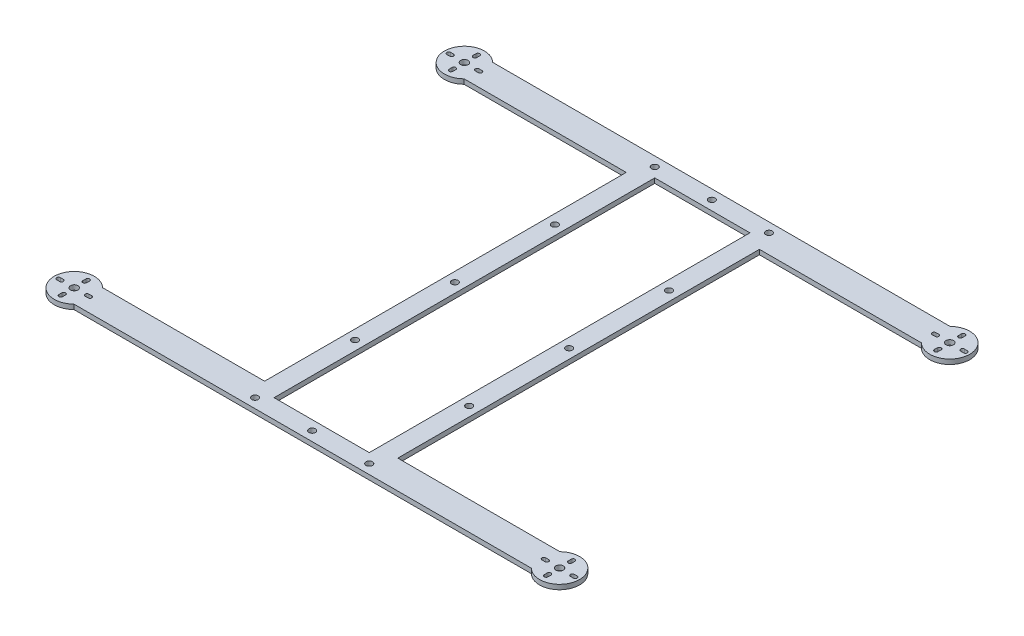
SolidWorks part; units mm, degrees
ref_plane "Front Plane" through (0, 0, 0) normal (0, 0, 1) x (1, 0, 0)
ref_plane "Top Plane" through (0, 0, 0) normal (0, 1, 0) x (1, 0, 0)
ref_plane "Right Plane" through (0, 0, 0) normal (1, 0, 0) x (0, 0, -1)
sketch "Sketch1" plane through (0, 0, 0) normal (0, 1, 0) x (1, 0, 0)
  line L1 (-44.45, 139.7) -> (44.45, 139.7)
  line L2 (-44.45, 120.65) -> (-44.45, -120.65)
  line L3 (-44.45, -139.7) -> (44.45, -139.7)
  line L4 (44.45, 120.65) -> (44.45, -120.65)
  line L5 (44.45, 139.7) -> (161.925, 139.7)
  line L7 (44.45, 120.65) -> (161.925, 120.65)
  line L8 (161.925, 139.7) -> (161.925, 120.65)
  line L14 (0, 0) -> (0, 187.5455) construction
  line L17 (0, 0) -> (-239.6804, 0) construction
  line L21 (0, 0) -> (44.45, 0) construction
  line L22 (-44.45, 120.65) -> (-161.925, 120.65)
  line L23 (-44.45, 139.7) -> (-161.925, 139.7)
  line L24 (-161.925, 139.7) -> (-161.925, 120.65)
  line L37 (-31.75, 127) -> (31.75, 127)
  line L40 (-31.75, 127) -> (-31.75, -127)
  line L43 (-31.75, -127) -> (31.75, -127)
  line L46 (31.75, 127) -> (31.75, -127)
  line L49 (44.45, -120.65) -> (161.925, -120.65)
  line L50 (44.45, -139.7) -> (161.925, -139.7)
  line L51 (161.925, -139.7) -> (161.925, -120.65)
  line L88 (-161.925, -139.7) -> (-161.925, -120.65)
  line L89 (-44.45, -139.7) -> (-161.925, -139.7)
  line L90 (-44.45, -120.65) -> (-161.925, -120.65)
  point P4 (0, 139.7)
  point P6 (-44.45, 0)
  dimension "D4" = 117.475
  dimension "D1" = 279.4
  dimension "D2" = 88.9
  dimension "D3" = 19.05
  dimension "D6" = 12.7
  dimension "D7" = 12.7
  dimension "D8" = 12.7
  dimension "D10" = 117.475
  dimension "D12" = 12.7
  dimension "D18" = 19.05
extrude "Boss-Extrude1" add sketch "Sketch1" along normal blind 3.175
sketch "Sketch4" plane through (0, 3.175, 0) normal (0, 1, 0) x (1, 0, 0)
  line L0 (161.925, 120.65) -> (161.925, 139.7) construction
  line L1 (-161.925, 139.7) -> (-161.925, 120.65) construction
  line L2 (-161.925, -120.65) -> (-161.925, -139.7) construction
  line L3 (161.925, -139.7) -> (161.925, -120.65) construction
  circle A0 centre (161.925, 130.175) radius 13.335
  circle A1 centre (-161.925, 130.175) radius 13.335
  circle A2 centre (-161.925, -130.175) radius 13.335
  circle A3 centre (161.925, -130.175) radius 13.335
  point P18 (161.925, -130.175)
extrude "Boss-Extrude4" add sketch "Sketch4" against normal up to surface (3.175 mm away) up to face at (0, 0, 0)
sketch "Sketch5" plane through (0, 3.175, 0) normal (0, 1, 0) x (1, 0, 0)
  line L0 (151.425, 130.175) -> (153.425, 130.175) construction
  line L1 (151.425, 131.425) -> (153.425, 131.425)
  line L2 (151.425, 128.925) -> (153.425, 128.925)
  line L3 (161.925, 130.175) -> (161.925, 143.51) construction
  line L4 (172.425, 130.175) -> (170.425, 130.175) construction
  line L5 (172.425, 131.425) -> (170.425, 131.425)
  line L6 (172.425, 128.925) -> (170.425, 128.925)
  line L7 (161.925, 139.175) -> (161.925, 137.175) construction
  line L8 (163.175, 139.175) -> (163.175, 137.175)
  line L9 (160.675, 139.175) -> (160.675, 137.175)
  line L10 (161.925, 130.175) -> (175.26, 130.175) construction
  line L11 (161.925, 121.175) -> (161.925, 123.175) construction
  line L12 (163.175, 121.175) -> (163.175, 123.175)
  line L13 (160.675, 121.175) -> (160.675, 123.175)
  line L14 (0, 0) -> (0, 263.0018) construction
  line L15 (0, 0) -> (558.7896, 0) construction
  line L16 (-151.425, 130.175) -> (-153.425, 130.175) construction
  line L17 (-151.425, 131.425) -> (-153.425, 131.425)
  line L18 (-151.425, 128.925) -> (-153.425, 128.925)
  line L19 (-172.425, 130.175) -> (-170.425, 130.175) construction
  line L20 (-172.425, 131.425) -> (-170.425, 131.425)
  line L21 (-172.425, 128.925) -> (-170.425, 128.925)
  line L22 (-161.925, 139.175) -> (-161.925, 137.175) construction
  line L23 (-163.175, 139.175) -> (-163.175, 137.175)
  line L24 (-160.675, 139.175) -> (-160.675, 137.175)
  line L25 (-161.925, 121.175) -> (-161.925, 123.175) construction
  line L26 (-163.175, 121.175) -> (-163.175, 123.175)
  line L27 (-160.675, 121.175) -> (-160.675, 123.175)
  line L28 (-161.925, 130.175) -> (-175.26, 130.175) construction
  line L29 (-161.925, 130.175) -> (-161.925, 143.51) construction
  line L30 (151.425, -130.175) -> (153.425, -130.175) construction
  line L31 (151.425, -131.425) -> (153.425, -131.425)
  line L32 (151.425, -128.925) -> (153.425, -128.925)
  line L33 (161.925, -139.175) -> (161.925, -137.175) construction
  line L34 (163.175, -139.175) -> (163.175, -137.175)
  line L35 (160.675, -139.175) -> (160.675, -137.175)
  line L36 (172.425, -130.175) -> (170.425, -130.175) construction
  line L37 (172.425, -131.425) -> (170.425, -131.425)
  line L38 (172.425, -128.925) -> (170.425, -128.925)
  line L39 (161.925, -121.175) -> (161.925, -123.175) construction
  line L40 (163.175, -121.175) -> (163.175, -123.175)
  line L41 (160.675, -121.175) -> (160.675, -123.175)
  line L42 (161.925, -130.175) -> (175.26, -130.175) construction
  line L43 (161.925, -130.175) -> (161.925, -143.51) construction
  line L44 (-161.925, -130.175) -> (-161.925, -143.51) construction
  line L45 (-161.925, -130.175) -> (-175.26, -130.175) construction
  line L46 (-161.925, -121.175) -> (-161.925, -123.175) construction
  line L47 (-163.175, -121.175) -> (-163.175, -123.175)
  line L48 (-160.675, -121.175) -> (-160.675, -123.175)
  line L49 (-161.925, -139.175) -> (-161.925, -137.175) construction
  line L50 (-163.175, -139.175) -> (-163.175, -137.175)
  line L51 (-160.675, -139.175) -> (-160.675, -137.175)
  line L52 (-172.425, -130.175) -> (-170.425, -130.175) construction
  line L53 (-172.425, -131.425) -> (-170.425, -131.425)
  line L54 (-172.425, -128.925) -> (-170.425, -128.925)
  line L55 (-151.425, -130.175) -> (-153.425, -130.175) construction
  line L56 (-151.425, -131.425) -> (-153.425, -131.425)
  line L57 (-151.425, -128.925) -> (-153.425, -128.925)
  circle A0 centre (161.925, 130.175) radius 2.5
  arc A1 (151.425, 131.425) -> (151.425, 128.925) centre (151.425, 130.175) ccw
  arc A2 (153.425, 128.925) -> (153.425, 131.425) centre (153.425, 130.175) ccw
  arc A3 (152.5924, 120.65) -> (152.5924, 139.7) centre (161.925, 130.175) ccw construction
  arc A4 (172.425, 131.425) -> (172.425, 128.925) centre (172.425, 130.175) cw
  arc A5 (170.425, 128.925) -> (170.425, 131.425) centre (170.425, 130.175) cw
  arc A6 (163.175, 139.175) -> (160.675, 139.175) centre (161.925, 139.175) ccw
  arc A7 (160.675, 137.175) -> (163.175, 137.175) centre (161.925, 137.175) ccw
  arc A8 (163.175, 121.175) -> (160.675, 121.175) centre (161.925, 121.175) cw
  arc A9 (160.675, 123.175) -> (163.175, 123.175) centre (161.925, 123.175) cw
  arc A10 (-151.425, 131.425) -> (-151.425, 128.925) centre (-151.425, 130.175) cw
  arc A11 (-153.425, 128.925) -> (-153.425, 131.425) centre (-153.425, 130.175) cw
  arc A12 (-172.425, 131.425) -> (-172.425, 128.925) centre (-172.425, 130.175) ccw
  arc A13 (-170.425, 128.925) -> (-170.425, 131.425) centre (-170.425, 130.175) ccw
  arc A14 (-163.175, 139.175) -> (-160.675, 139.175) centre (-161.925, 139.175) cw
  arc A15 (-160.675, 137.175) -> (-163.175, 137.175) centre (-161.925, 137.175) cw
  arc A16 (-163.175, 121.175) -> (-160.675, 121.175) centre (-161.925, 121.175) ccw
  arc A17 (-160.675, 123.175) -> (-163.175, 123.175) centre (-161.925, 123.175) ccw
  circle A18 centre (-161.925, 130.175) radius 2.5
  arc A19 (151.425, -131.425) -> (151.425, -128.925) centre (151.425, -130.175) cw
  arc A20 (153.425, -128.925) -> (153.425, -131.425) centre (153.425, -130.175) cw
  arc A21 (163.175, -139.175) -> (160.675, -139.175) centre (161.925, -139.175) cw
  arc A22 (160.675, -137.175) -> (163.175, -137.175) centre (161.925, -137.175) cw
  arc A23 (172.425, -131.425) -> (172.425, -128.925) centre (172.425, -130.175) ccw
  arc A24 (170.425, -128.925) -> (170.425, -131.425) centre (170.425, -130.175) ccw
  arc A25 (163.175, -121.175) -> (160.675, -121.175) centre (161.925, -121.175) ccw
  arc A26 (160.675, -123.175) -> (163.175, -123.175) centre (161.925, -123.175) ccw
  circle A27 centre (161.925, -130.175) radius 2.5
  circle A28 centre (-161.925, -130.175) radius 2.5
  arc A29 (-163.175, -121.175) -> (-160.675, -121.175) centre (-161.925, -121.175) cw
  arc A30 (-160.675, -123.175) -> (-163.175, -123.175) centre (-161.925, -123.175) cw
  arc A31 (-163.175, -139.175) -> (-160.675, -139.175) centre (-161.925, -139.175) ccw
  arc A32 (-160.675, -137.175) -> (-163.175, -137.175) centre (-161.925, -137.175) ccw
  arc A33 (-172.425, -131.425) -> (-172.425, -128.925) centre (-172.425, -130.175) cw
  arc A34 (-170.425, -128.925) -> (-170.425, -131.425) centre (-170.425, -130.175) cw
  arc A35 (-151.425, -131.425) -> (-151.425, -128.925) centre (-151.425, -130.175) ccw
  arc A36 (-153.425, -128.925) -> (-153.425, -131.425) centre (-153.425, -130.175) ccw
  point P5 (152.425, 130.175)
  point P16 (171.425, 130.175)
  point P23 (161.925, 138.175)
  point P31 (161.925, 122.175)
  point P42 (-152.425, 130.175)
  point P49 (-171.425, 130.175)
  point P56 (-161.925, 138.175)
  point P63 (-161.925, 122.175)
  point P74 (152.425, -130.175)
  point P81 (161.925, -138.175)
  point P88 (171.425, -130.175)
  point P95 (161.925, -122.175)
  point P110 (-161.925, -122.175)
  point P117 (-161.925, -138.175)
  point P124 (-171.425, -130.175)
  point P131 (-152.425, -130.175)
  dimension "D1" = 5
  dimension "D2" = 2.5
  dimension "D3" = 2
  dimension "D4" = 19
  dimension "D5" = 2.5
  dimension "D6" = 2
  dimension "D7" = 16
extrude "Motor Holes" cut sketch "Sketch5" against normal through all
sketch "Sketch7" plane through (0, 3.175, 0) normal (0, 1, 0) x (1, 0, 0)
  line L0 (152.5924, 139.7) -> (-152.5924, 139.7) construction
  line L1 (-44.45, 120.65) -> (-44.45, -120.65) construction
  line L2 (0, 0) -> (0, 246.0772) construction
  line L3 (0, 0) -> (301.4392, 0) construction
  circle A0 centre (-38.1, 133.35) radius 2.159
  circle A1 centre (-38.1, 66.675) radius 2.159
  circle A2 centre (-38.1, 0) radius 2.159
  circle A3 centre (-38.1, -66.675) radius 2.159
  circle A5 centre (-38.1, -133.35) radius 2.159
  circle A6 centre (38.1, -133.35) radius 2.159
  circle A7 centre (38.1, -66.675) radius 2.159
  circle A8 centre (38.1, 0) radius 2.159
  circle A9 centre (38.1, 66.675) radius 2.159
  circle A10 centre (38.1, 133.35) radius 2.159
  circle A11 centre (0, 133.35) radius 2.159
  circle A12 centre (0, -133.35) radius 2.159
  dimension "D1" = 4.318
  dimension "D2" = 6.35
  dimension "D3" = 6.35
  dimension "D4" = 66.675
  dimension "D5" = 66.675
  dimension "D6" = 66.675
  dimension "D7" = 66.675
extrude "Cut-Extrude2" cut sketch "Sketch7" against normal through all
